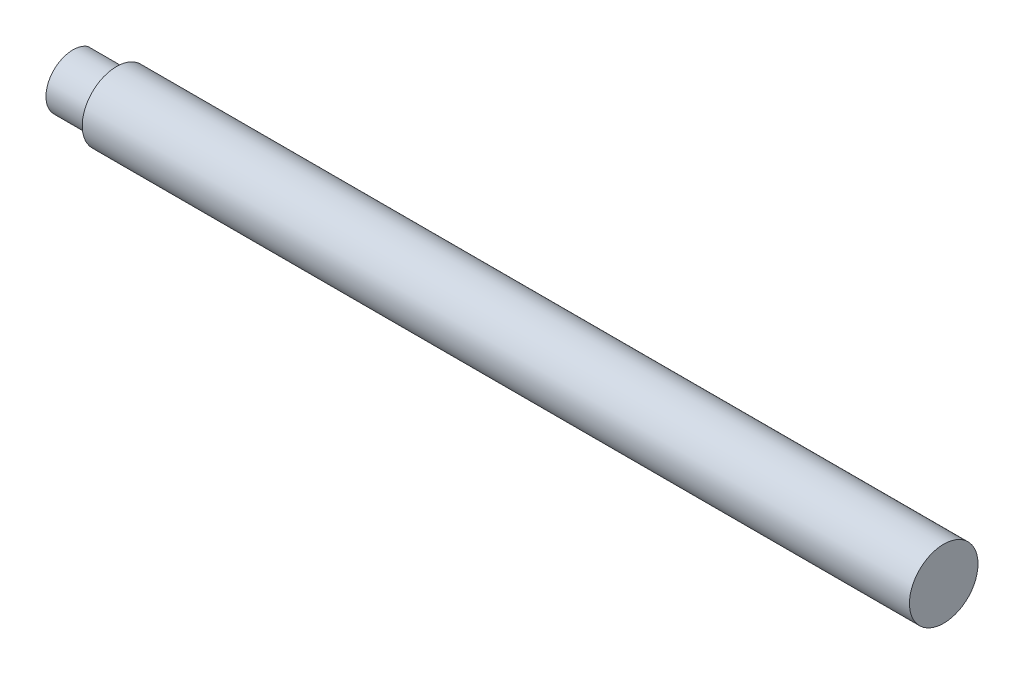
SolidWorks part; units mm, degrees
material "Plain Carbon Steel"
ref_plane "Front Plane" through (0, 0, 0) normal (0, 0, 1) x (1, 0, 0)
ref_plane "Top Plane" through (0, 0, 0) normal (0, 1, 0) x (1, 0, 0)
ref_plane "Right Plane" through (0, 0, 0) normal (1, 0, 0) x (0, 0, -1)
sketch "Sketch1" plane through (0, 0, 0) normal (1, 0, 0) x (0, 0, -1)
  circle A0 centre (0, 0) radius 2.5
  dimension "D1" = 5
extrude "Base" add sketch "Sketch1" along normal blind 63.5
sketch "Sketch2" plane through (0, 0, 0) normal (1, 0, 0) x (0, 0, -1)
  line L0 (1.0795, 1.6461) -> (1.0795, -1.6461)
  arc A0 (1.0795, 1.6461) -> (1.0795, -1.6461) centre (0, 0) ccw
  dimension "D1" = 3.937
  dimension "D2" = 1.0795
extrude "Cut-Extrude1" cut sketch "Sketch2" along normal blind 3.175 flip side to cut
